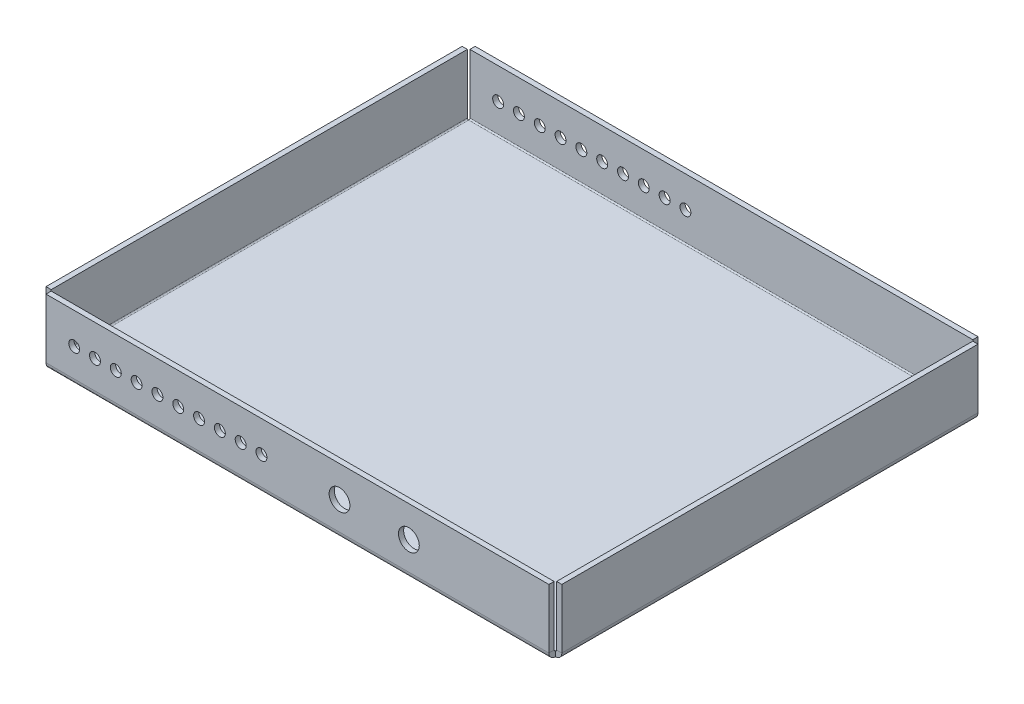
SolidWorks part; units mm, degrees
note: The reader was unsure of these and kept them because the rebuilt part matched: flange length of "Edge-Flange1", "Edge-Flange2", "Edge-Flange3", "Edge-Flange4".
other "Weld Folder"
material "1060 Alloy"
ref_plane "Front Plane" through (0, 0, 0) normal (0, 0, 1) x (1, 0, 0)
ref_plane "Top Plane" through (0, 0, 0) normal (0, 1, 0) x (1, 0, 0)
ref_plane "Right Plane" through (0, 0, 0) normal (1, 0, 0) x (0, 0, -1)
sketch "Sketch15" plane through (0, 0, 0) normal (0, 1, 0) x (1, 0, 0)
  line L1 (0, 0) -> (290, 0)
  line L2 (0, 0) -> (0, 240)
  line L3 (0, 240) -> (290, 240)
  line L4 (290, 0) -> (290, 240)
  dimension "D1" = 290
  dimension "D2" = 240
base flange "Base-Flange1" sketch "Sketch15" thickness 3 reverse thickness direction no parameters "D1"=0.7366
edge flange "Edge-Flange1" sketch "Sketch22" flange angle 90 flange length 35 flange position bend outside bend radius 0.7366 thickness 3 relief rectangular parameters "D6"=10
sketch "Sketch22" plane through (0, 0, 0) normal (-1, 0, 0) x (0, 0, 1)
  line L2 (-240, 0) -> (-240, 35)
  line L3 (-240, 35) -> (0, 35)
  line L4 (0, 35) -> (0, 0)
  line L7 (-240, 0) -> (0, 0) construction
  line L8 (-240, 0) -> (0, 0)
bend "EdgeBend1" bend radius 0.7366 bend angle 90 parameters "D5"=1
edge flange "Edge-Flange2" sketch "Sketch25" flange angle 90 flange length 35 flange position bend outside bend radius 0.7366 thickness 3 relief rectangular parameters "D6"=10
sketch "Sketch25" plane through (0, 0, 0) normal (0, 0, 1) x (1, 0, 0)
  line L0 (0, 0) -> (290, 0) construction
  line L1 (0, 0) -> (290, 0)
  line L2 (0, 0) -> (0, 35)
  line L3 (0, 35) -> (290, 35)
  line L4 (290, 35) -> (290, 0)
bend "EdgeBend2" bend radius 0.7366 bend angle 90 parameters "D5"=2
edge flange "Edge-Flange3" sketch "Sketch28" flange angle 90 flange length 35 flange position bend outside bend radius 0.7366 thickness 3 relief rectangular parameters "D6"=10
sketch "Sketch28" plane through (290, 0, 0) normal (1, 0, 0) x (0, 0, -1)
  line L0 (0, 0) -> (240, 0) construction
  line L1 (0, 0) -> (240, 0)
  line L2 (0, 0) -> (0, 35)
  line L3 (0, 35) -> (240, 35)
  line L4 (240, 35) -> (240, 0)
bend "EdgeBend3" bend radius 0.7366 bend angle 90 parameters "D5"=3
edge flange "Edge-Flange4" sketch "Sketch31" flange angle 90 flange length 35 flange position bend outside bend radius 0.7366 thickness 3 relief rectangular parameters "D6"=10
sketch "Sketch31" plane through (0, 0, -240) normal (0, 0, -1) x (-1, 0, 0)
  line L2 (-290, 0) -> (-290, 35)
  line L3 (-290, 35) -> (0, 35)
  line L4 (0, 35) -> (0, 0)
  line L15 (-290, 0) -> (0, 0) construction
  line L16 (-290, 0) -> (0, 0)
bend "EdgeBend4" bend radius 0.7366 bend angle 90 parameters "D5"=4
sketch "Sketch32" plane through (0, 0, 3.7366) normal (0, 0, 1) x (1, 0, 0)
  line L0 (290, -3) -> (0, -3) construction
  line L1 (-3.7366, 0.7366) -> (-3.7366, 35) construction
  circle A0 centre (16.2634, 17) radius 3.15
  circle A1 centre (28.2634, 17) radius 3.15
  circle A2 centre (40.2634, 17) radius 3.15
  circle A3 centre (52.2634, 17) radius 3.15
  circle A4 centre (64.2634, 17) radius 3.15
  circle A5 centre (76.2634, 17) radius 3.15
  circle A6 centre (88.2634, 17) radius 3.15
  circle A7 centre (100.2634, 17) radius 3.15
  circle A8 centre (112.2634, 17) radius 3.15
  circle A9 centre (124.2634, 17) radius 3.15
  dimension "D1" = 6.3
  dimension "D3" = 20
  dimension "D5" = 12
  dimension "D2" = 20
  dimension "D4" = 10
extrude "Cut-Extrude3" cut sketch "Sketch32" against normal through all normal cut yes
sketch "Sketch33" plane through (0, 0, 3.7366) normal (0, 0, 1) x (1, 0, 0)
  line L0 (97.1134, 17) -> (233.3781, 17) construction
  circle A0 centre (100.2634, 17) radius 3.15 construction
  circle A1 centre (169.2634, 17) radius 6
  circle A2 centre (209.2634, 17) radius 6
  circle A3 centre (124.2634, 17) radius 3.15 construction
  dimension "D1" = 12
  dimension "D2" = 45
  dimension "D3" = 40
  dimension "D4" = 12
extrude "Cut-Extrude4" cut sketch "Sketch33" against normal blind 10 normal cut yes
sketch "Bend-Lines1" [suppressed] plane through (0, 0, 0) normal (0, 1, 0) x (1, 0, 0)
sketch "Bounding-Box1" [suppressed] plane through (0, 0, 0) normal (0, 1, 0) x (1, 0, 0)
sheet metal parameters "Sheet-Metal10" thickness 3 parameters "D1"=0.7366
flat pattern "Flat-Pattern10" [suppressed]
sketch "Bend-Lines2" plane through (0, 0, 0) normal (0, 1, 0) x (1, 0, 0)
sketch3d "Bounding-Box2" [suppressed]
  line L0 (-250, 200, 0) -> (0, 200, 0) construction
  line L1 (-250, 0, 0) -> (0, 0, 0) construction
  line L2 (-250, 200, 0) -> (-250, 0, 0) construction
  line L3 (0, 200, 0) -> (0, 0, 0) construction
sheet metal parameters "Sheet-Metal11" thickness 3 parameters "D1"=0.7366
flat pattern "Flat-Pattern10"
sketch "Bend-Lines2" plane through (0, 0, 0) normal (0, 1, 0) x (1, 0, 0)
  line L0 (-1.2556, 200) -> (-1.2556, 0) construction
  line L1 (-1.2556, 200) -> (-1.2556, 0) construction
sketch3d "Bounding-Box2" [suppressed]
  line L0 (250, 200, 0) -> (-32.5113, 200, 0) construction
  line L1 (250, 0, 0) -> (-32.5113, 0, 0) construction
  line L2 (250, 200, 0) -> (250, 0, 0) construction
  line L3 (-32.5113, 200, 0) -> (-32.5113, 0, 0) construction
bend of the flat pattern "Flatten-<EdgeBend1>1"
sheet metal parameters "Sheet-Metal12" thickness 3 parameters "D1"=0.7366
flat pattern "Flat-Pattern10"
sketch "Bend-Lines2" plane through (0, 0, 0) normal (0, 1, 0) x (1, 0, 0)
  line L0 (-1.2556, 200) -> (-1.2556, 0) construction
  line L1 (-1.2556, 200) -> (-1.2556, 0) construction
  line L2 (0.7366, -1.2556) -> (250, -1.2556) construction
  line L3 (0.7366, -1.2556) -> (250, -1.2556) construction
sketch3d "Bounding-Box2" [suppressed]
  line L0 (250, 200, 0) -> (-32.5113, 200, 0) construction
  line L1 (250, -32.5113, 0) -> (-32.5113, -32.5113, 0) construction
  line L2 (250, 200, 0) -> (250, -32.5113, 0) construction
  line L3 (-32.5113, 200, 0) -> (-32.5113, -32.5113, 0) construction
bend of the flat pattern "Flatten-<EdgeBend1>1"
bend of the flat pattern "Flatten-<EdgeBend2>1"
sheet metal parameters "Sheet-Metal13" thickness 3 parameters "D1"=0.7366
flat pattern "Flat-Pattern10"
sketch "Bend-Lines2" plane through (0, 0, 0) normal (0, 1, 0) x (1, 0, 0)
  line L0 (-1.2556, 200) -> (-1.2556, 0) construction
  line L1 (-1.2556, 200) -> (-1.2556, 0) construction
  line L2 (0.7366, -1.2556) -> (250, -1.2556) construction
  line L3 (0.7366, -1.2556) -> (250, -1.2556) construction
  line L4 (251.2556, 0.7366) -> (251.2556, 200) construction
  line L5 (251.2556, 0.7366) -> (251.2556, 200) construction
sketch3d "Bounding-Box2" [suppressed]
  line L0 (282.5113, 200, 0) -> (-32.5113, 200, 0) construction
  line L1 (282.5113, -32.5113, 0) -> (-32.5113, -32.5113, 0) construction
  line L2 (282.5113, 200, 0) -> (282.5113, -32.5113, 0) construction
  line L3 (-32.5113, 200, 0) -> (-32.5113, -32.5113, 0) construction
bend of the flat pattern "Flatten-<EdgeBend1>1"
bend of the flat pattern "Flatten-<EdgeBend2>1"
bend of the flat pattern "Flatten-<EdgeBend3>1"
sheet metal parameters "Sheet-Metal14" thickness 3 parameters "D1"=0.7366
flat pattern "Flat-Pattern10"
sketch "Bend-Lines2" plane through (0, 0, 0) normal (0, 1, 0) x (1, 0, 0)
  line L0 (-1.2556, 200) -> (-1.2556, 0) construction
  line L1 (-1.2556, 200) -> (-1.2556, 0) construction
  line L2 (0.7366, -1.2556) -> (250, -1.2556) construction
  line L3 (0.7366, -1.2556) -> (250, -1.2556) construction
  line L4 (251.2556, 0.7366) -> (251.2556, 200) construction
  line L5 (251.2556, 0.7366) -> (251.2556, 200) construction
  line L6 (249.2634, 201.2556) -> (0.7366, 201.2556) construction
  line L7 (249.2634, 201.2556) -> (0.7366, 201.2556) construction
sketch3d "Bounding-Box2" [suppressed]
  line L0 (282.5113, 232.5113, 0) -> (-32.5113, 232.5113, 0) construction
  line L1 (282.5113, -32.5113, 0) -> (-32.5113, -32.5113, 0) construction
  line L2 (282.5113, 232.5113, 0) -> (282.5113, -32.5113, 0) construction
  line L3 (-32.5113, 232.5113, 0) -> (-32.5113, -32.5113, 0) construction
bend of the flat pattern "Flatten-<EdgeBend1>1"
bend of the flat pattern "Flatten-<EdgeBend2>1"
bend of the flat pattern "Flatten-<EdgeBend3>1"
bend of the flat pattern "Flatten-<EdgeBend4>1"
sheet metal parameters "Sheet-Metal15" thickness 3 parameters "D1"=0.7366
flat pattern "Flat-Pattern10"
sketch "Bend-Lines2" plane through (0, 0, 0) normal (0, 1, 0) x (1, 0, 0)
  line L0 (-1.9922, 240) -> (-1.9922, 0) construction
  line L1 (-1.9922, 240) -> (-1.9922, 0) construction
  line L2 (0, -1.9922) -> (290, -1.9922) construction
  line L3 (0, -1.9922) -> (290, -1.9922) construction
  line L4 (291.9922, 0) -> (291.9922, 240) construction
  line L5 (291.9922, 0) -> (291.9922, 240) construction
  line L6 (290, 241.9922) -> (0, 241.9922) construction
  line L7 (290, 241.9922) -> (0, 241.9922) construction
sketch3d "Bounding-Box2" [suppressed]
  line L0 (328.2479, 278.2479, 0) -> (-38.2479, 278.2479, 0) construction
  line L1 (328.2479, -38.2479, 0) -> (-38.2479, -38.2479, 0) construction
  line L2 (328.2479, 278.2479, 0) -> (328.2479, -38.2479, 0) construction
  line L3 (-38.2479, 278.2479, 0) -> (-38.2479, -38.2479, 0) construction
bend of the flat pattern "Flatten-<EdgeBend1>1"
bend of the flat pattern "Flatten-<EdgeBend2>1"
bend of the flat pattern "Flatten-<EdgeBend3>1"
bend of the flat pattern "Flatten-<EdgeBend4>1"
sheet metal parameters "Sheet-Metal16" thickness 3 parameters "D1"=0.7366
flat pattern "Flat-Pattern10"
sketch "Bend-Lines2" plane through (0, 0, 0) normal (0, 1, 0) x (1, 0, 0)
  line L0 (-1.9922, 240) -> (-1.9922, 0) construction
  line L1 (-1.9922, 240) -> (-1.9922, 0) construction
  line L2 (0, -1.9922) -> (290, -1.9922) construction
  line L3 (0, -1.9922) -> (290, -1.9922) construction
  line L4 (291.9922, 0) -> (291.9922, 240) construction
  line L5 (291.9922, 0) -> (291.9922, 240) construction
  line L6 (290, 241.9922) -> (0, 241.9922) construction
  line L7 (290, 241.9922) -> (0, 241.9922) construction
sketch3d "Bounding-Box2" [suppressed]
  line L0 (328.2479, 278.2479, 0) -> (-38.2479, 278.2479, 0) construction
  line L1 (328.2479, -38.2479, 0) -> (-38.2479, -38.2479, 0) construction
  line L2 (328.2479, 278.2479, 0) -> (328.2479, -38.2479, 0) construction
  line L3 (-38.2479, 278.2479, 0) -> (-38.2479, -38.2479, 0) construction
bend of the flat pattern "Flatten-<EdgeBend1>1"
bend of the flat pattern "Flatten-<EdgeBend2>1"
bend of the flat pattern "Flatten-<EdgeBend3>1"
bend of the flat pattern "Flatten-<EdgeBend4>1"
